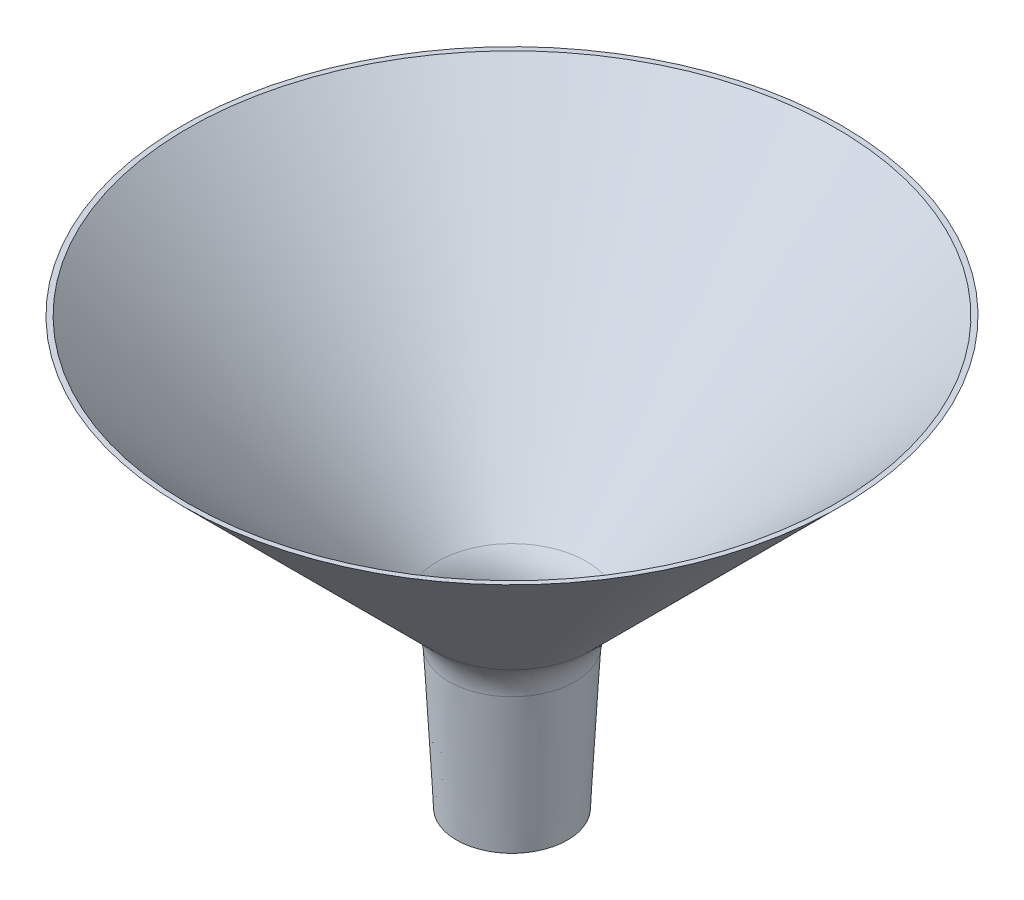
SolidWorks part; units mm, degrees
ref_plane "Front Plane" through (0, 0, 0) normal (0, 0, 1) x (1, 0, 0)
ref_plane "Top Plane" through (0, 0, 0) normal (0, 1, 0) x (1, 0, 0)
ref_plane "Right Plane" through (0, 0, 0) normal (1, 0, 0) x (0, 0, -1)
sketch "Sketch1" plane through (0, 0, 0) normal (0, 0, 1) x (1, 0, 0)
  line L0 (0, 0) -> (8, 0) construction
  line L1 (8, 0) -> (9.3102, 25)
  line L2 (9.3102, 25) -> (50, 65.6898)
  line L3 (50, 65.6898) -> (50.7778, 65.6898)
  line L4 (50.7778, 65.6898) -> (9.8484, 24.7604)
  line L5 (9.8484, 24.7604) -> (8.5508, 0)
  line L6 (8.5508, 0) -> (8, 0)
  line L7 (30.3131, 45.2251) -> (29.9242, 45.614) construction
  line L8 (9.1996, 12.3802) -> (8.6503, 12.409) construction
  line L9 (0, 0.7781) -> (0, 50000.7781) construction
  line L10 (9.3102, 25) -> (0, 25) construction
  line L11 (8.5508, 0) -> (8.5508, 25) construction
  dimension "D2" = 8
  dimension "D1" = 0.55
  dimension "D3" = 50
  dimension "D5" = 45
  dimension "D4" = 25
  dimension "D6" = 93
  dimension "D7" = 65.6898
ref_axis "Axis1" through (0, -2.9, 0) along (0, 1, 0)
revolve "Revolve1" add sketch "Sketch1" angle 360 about axis through (0, -2.9, 0) along (0, 1, 0)
fillet "Fillet1" radius 8 1 edges at (0, 24.7604, -9.8484)
fillet "Fillet2" radius 8 1 edges at (0, 25, -9.3102)
equation "\"Spout_Tip\" = 8'Radius"
equation "\"D2@Sketch1\"=\"Spout_Tip\""
equation "\"Funnel_Enterance\"= 50'Radius"
equation "\"D3@Sketch1\"=\"Funnel_Enterance\""
equation "\"Spout_Length\"= 25"
equation "\"D4@Sketch1\"=\"Spout_Length\""
